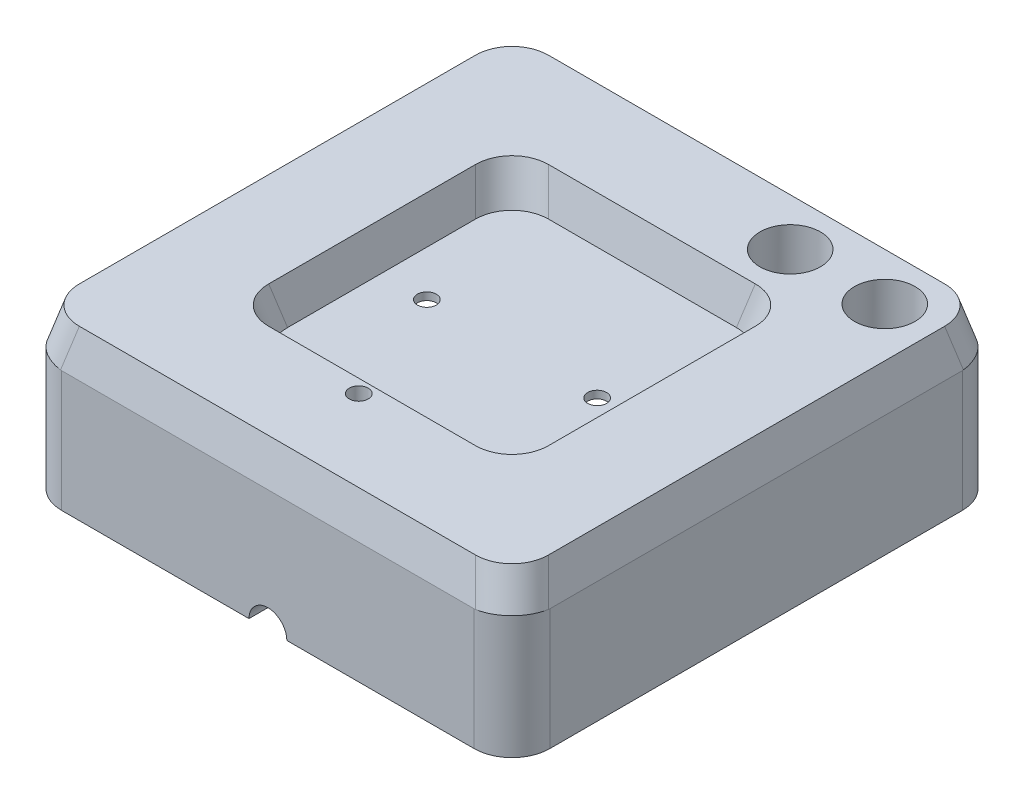
SolidWorks part; units mm, degrees
ref_plane "Front Plane" through (0, 0, 0) normal (0, 0, 1) x (1, 0, 0)
ref_plane "Top Plane" through (0, 0, 0) normal (0, 1, 0) x (1, 0, 0)
ref_plane "Right Plane" through (0, 0, 0) normal (1, 0, 0) x (0, 0, -1)
sketch "Sketch1" plane through (0, 0, 0) normal (0, 1, 0) x (1, 0, 0)
  line L1 (-34.5, -34.5) -> (34.5, -34.5)
  line L2 (-34.5, -34.5) -> (-34.5, 34.5)
  line L3 (-34.5, 34.5) -> (34.5, 34.5)
  line L4 (34.5, -34.5) -> (34.5, 34.5)
  line L5 (-34.5, -34.5) -> (34.5, 34.5) construction
  line L6 (-34.5, 34.5) -> (34.5, -34.5) construction
  point P0 (0, 0)
  dimension "D1" = 69
ref_plane "Plane1" through (0, 10, 0) normal (0, 1, 0) x (1, 0, 0)
extrude "Extrude-Thin1" add sketch "Sketch1" along normal blind 10 draft 14 thin thin type one direction wall 30
fillet "Fillet1" radius 10 4 edges at (35.7466, 5, 35.7466) (35.7466, 5, -35.7466) (-35.7466, 5, -35.7466) (-35.7466, 5, 35.7466)
sketch "Sketch3" plane through (0, 0, 0) normal (0, -1, 0) x (1, 0, 0)
  line L4 (64.5, -64.5) -> (64.5, 64.5)
  line L5 (64.5, 64.5) -> (-64.5, 64.5)
  line L6 (-64.5, 64.5) -> (-64.5, -64.5)
  line L7 (-64.5, -64.5) -> (64.5, -64.5)
  line L8 (64.5, -64.5) -> (64.5, 64.5)
  line L9 (64.5, 64.5) -> (-64.5, 64.5)
  line L10 (-64.5, 64.5) -> (-64.5, -64.5)
  line L11 (-64.5, -64.5) -> (64.5, -64.5)
  dimension "D1" = 0
extrude "Boss-Extrude1" add sketch "Sketch3" along normal blind 2
sketch "Sketch4" plane through (0, 0, 0) normal (0, 1, 0) x (1, 0, 0)
  line L0 (-2.9848, 0) -> (-16.8616, 0) construction
  circle A0 centre (-22.5, 0) radius 2.5
  dimension "D1" = 5
  dimension "D2" = 22.5
extrude "Cut-Extrude1" cut sketch "Sketch4" against normal up to surface (2 mm away) up to face at (0, -2, 0)
ref_plane "Plane2" through (0, 0, 0) normal (1, 0, 0) x (0, 0, -1)
mirror "Mirror1" about plane through (0, 0, 0) normal (1, 0, 0) of "Cut-Extrude1"
sketch "Sketch5" plane through (0, -2, 0) normal (0, -1, 0) x (1, 0, 0)
  line L1 (-64.5, -64.5) -> (64.5, -64.5) construction
  line L2 (64.5, -64.5) -> (64.5, 64.5) construction
  line L3 (64.5, 64.5) -> (-64.5, 64.5) construction
  line L4 (-64.5, 64.5) -> (-64.5, -64.5) construction
  line L5 (-64.5, -64.5) -> (64.5, -64.5)
  line L6 (64.5, -64.5) -> (64.5, 64.5)
  line L7 (64.5, 64.5) -> (-64.5, 64.5)
  line L8 (-64.5, 64.5) -> (-64.5, -64.5)
extrude "Extrude-Thin2" add sketch "Sketch5" along normal blind 30 thin thin type one direction reverse wall 5
sketch "Sketch6" plane through (0, 0, 64.5) normal (0, 0, 1) x (1, 0, 0)
  line L0 (64.5, -32) -> (-64.5, -32) construction
  line L1 (-5, -32) -> (5, -32)
  arc A0 (-5, -32) -> (5, -32) centre (0, -32) cw
  dimension "D1" = 5
extrude "Cut-Extrude2" cut sketch "Sketch6" against normal up to surface (5 mm away) up to face at (0, -17, 59.5)
sketch "Sketch7" plane through (0, 10, 0) normal (0, 1, 0) x (1, 0, 0)
  line L0 (0, -23.1) -> (0, 23.1) construction
  line L2 (-27.2903, -36.9933) -> (27.2903, -36.9933) construction
  circle A0 centre (0, -40.4933) radius 2.5
  dimension "D1" = 5
  dimension "D2" = 3.5
extrude "Cut-Extrude3" cut sketch "Sketch7" against normal up to surface (12 mm away) up to face at (0, -2, 0)
fillet "Fillet2" radius 10 8 edges at (-63.2534, 5, 63.2534) (-64.5, -16, 64.5) (64.5, -16, 64.5) (63.2534, 5, 63.2534) (63.2534, 5, -63.2534) (64.5, -16, -64.5) (-64.5, -16, -64.5) (-63.2534, 5, -63.2534)
sketch "Sketch8" plane through (0, 0, -64.5) normal (0, 0, -1) x (-1, 0, 0)
  line L0 (0, 23.1) -> (0, -23.1) construction
  line L1 (-39.5, -22) -> (39.5, -22)
  line L2 (-39.5, -22) -> (-39.5, -17)
  line L3 (-39.5, -17) -> (39.5, -17)
  line L4 (39.5, -22) -> (39.5, -17)
  line L5 (-39.5, -22) -> (39.5, -17) construction
  line L6 (-39.5, -17) -> (39.5, -22) construction
  line L7 (-54.5, 0) -> (-54.5, -32) construction
  line L8 (54.5, -32) -> (-54.5, -32) construction
  point P0 (0, -19.5)
  dimension "D1" = 5
  dimension "D2" = 15
  dimension "D3" = 10
extrude "Cut-Extrude4" cut sketch "Sketch8" against normal up to surface (5 mm away) up to face at (0, -17, -59.5)
sketch "Sketch9" plane through (0, 10, 0) normal (0, 1, 0) x (1, 0, 0)
  line L0 (52.3038, 62.0067) -> (-52.3038, 62.0067) construction
  line L1 (62.0067, -52.3038) -> (62.0067, 52.3038) construction
  line L3 (27.2903, 62.0067) -> (27.2903, 36.9933) construction
  line L4 (27.2903, 36.9933) -> (-27.2903, 36.9933) construction
  circle A0 centre (49.0067, 49.5) radius 8
  circle A1 centre (24.0067, 49.5) radius 8
  point P8 (27.2903, 49.5)
  point P13 (0, 0)
  point P14 (0, 0)
  dimension "D1" = 16
  dimension "D4" = 16
  dimension "D3" = 13
  dimension "D5" = 25
extrude "Cut-Extrude5" cut sketch "Sketch9" against normal up to surface (12 mm away) contours A0 up to face at (0, -2, 37.9933)
extrude "Cut-Extrude6" cut sketch "Sketch9<3>" against normal up to surface (12 mm away) up to face at (49.0067, -2, -57.5)
sketch "Sketch9<3>" plane through (0, 10, 0) normal (0, 1, 0) x (1, 0, 0) same geometry as "Sketch9"
